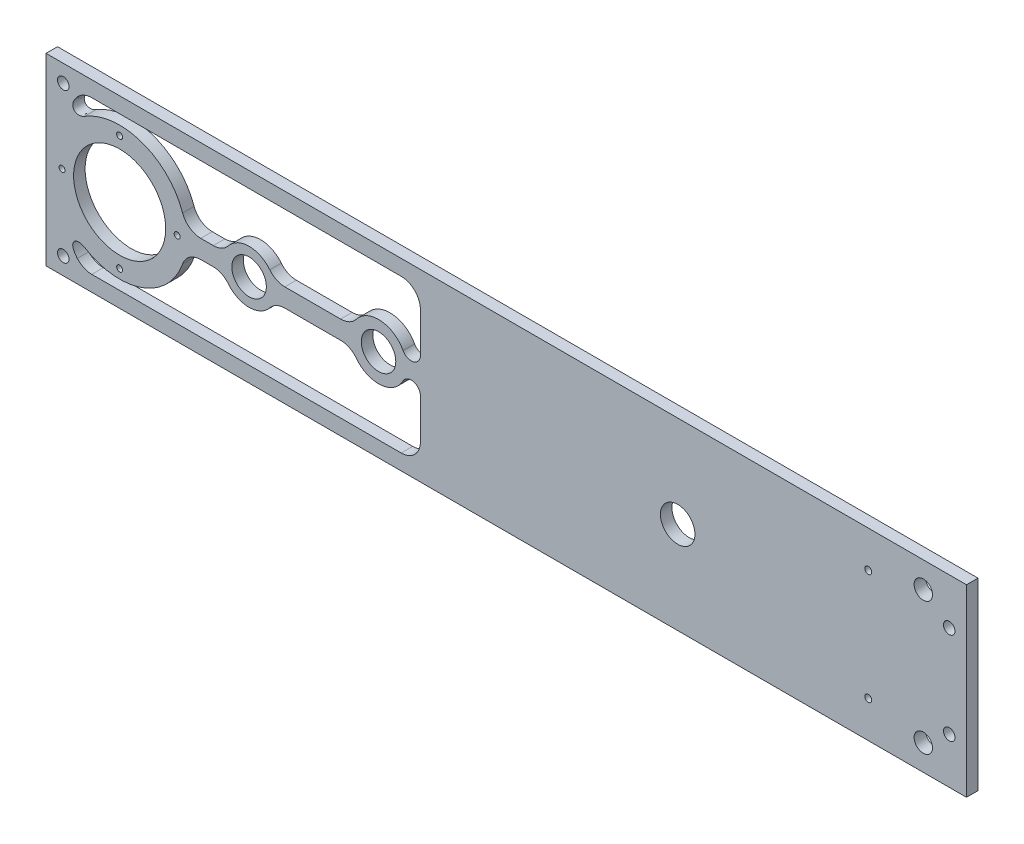
SolidWorks part; units mm, degrees
material "1060 Alloy"
ref_plane "Front Plane" through (0, 0, 0) normal (0, 0, 1) x (1, 0, 0)
ref_plane "Top Plane" through (0, 0, 0) normal (0, 1, 0) x (1, 0, 0)
ref_plane "Right Plane" through (0, 0, 0) normal (1, 0, 0) x (0, 0, -1)
sketch "Sketch1" plane through (0, 0, 0) normal (0, 0, 1) x (1, 0, 0)
  line L1 (0, 50.8) -> (508, 50.8)
  line L2 (0, 50.8) -> (0, -50.8)
  line L3 (0, -50.8) -> (508, -50.8)
  line L4 (508, 50.8) -> (508, -50.8)
  dimension "D1" = 508
  dimension "D2" = 101.6
extrude "Boss-Extrude1" add sketch "Sketch1" against normal blind 6.35
sketch "Sketch2" plane through (0, 0, 0) normal (0, 0, 1) x (1, 0, 0)
  line L0 (0, 50.8) -> (0, -50.8) construction
  circle A0 centre (40.64, 0) radius 25.4
  circle A1 centre (72.39, 0) radius 1.651
  circle A2 centre (40.64, -31.75) radius 1.651
  circle A3 centre (8.89, 0) radius 1.651
  circle A4 centre (40.64, 31.75) radius 1.651
  point P15 (40.64, 0)
  dimension "D1" = 50.8
  dimension "D2" = 3.302
  dimension "D3" = 31.75
  dimension "D4" = 40.64
  dimension "D5" = 4
extrude "Motor mount" cut sketch "Sketch2" against normal blind 6.35
sketch "Sketch3" plane through (0, 0, 0) normal (0, 0, 1) x (1, 0, 0)
  line L0 (398.315, 0) -> (50398.315, 0) construction
  circle A0 centre (40.64, 0) radius 25.4 construction
  circle A1 centre (40.64, 0) radius 25.4 construction
  circle A2 centre (112.0775, 0) radius 9.525
  circle A3 centre (183.515, 0) radius 9.525
  circle A4 centre (348.615, 0) radius 9.525
  circle A5 centre (453.8064, -30.5822) radius 47.9695 construction
  circle A6 centre (484.1695, -36.5735) radius 93.3199 construction
  circle A7 centre (453.8064, -30.5822) radius 47.9695 construction
  circle A8 centre (484.1695, -36.5735) radius 93.3199 construction
  circle A9 centre (453.8064, -30.5822) radius 1.905
  circle A10 centre (484.1695, -36.5735) radius 5.08
  circle A11 centre (484.1695, 36.5735) radius 5.08
  circle A12 centre (453.8064, 30.5822) radius 1.905
  dimension "D1" = 19.05
  dimension "D2" = 19.05
  dimension "D5" = 19.05
  dimension "D7" = 10.16
  dimension "D8" = 3.81
  dimension "D3" = 71.4375
  dimension "D4" = 71.4375
  dimension "D6" = 165.1
extrude "Cut-Extrude2" cut sketch "Sketch3" against normal through all
sketch "Sketch4" plane through (0, 0, 0) normal (0, 0, 1) x (1, 0, 0)
  line L0 (508, 50.8) -> (0, 50.8) construction
  line L1 (0, 50.8) -> (0, -50.8) construction
  line L2 (508, -50.8) -> (508, 50.8) construction
  line L3 (0, -50.8) -> (508, -50.8) construction
  circle A0 centre (9.525, 41.275) radius 3.175
  circle A1 centre (9.525, -41.275) radius 3.175
  circle A2 centre (498.475, 25.4) radius 3.175
  circle A3 centre (498.475, -25.4) radius 3.175
  dimension "D1" = 6.35
  dimension "D2" = 6.35
  dimension "D3" = 6.35
  dimension "D4" = 6.35
  dimension "D5" = 9.525
  dimension "D6" = 9.525
  dimension "D7" = 9.525
  dimension "D8" = 25.4
  dimension "D9" = 9.525
  dimension "D10" = 25.4
extrude "Cut-Extrude3" cut sketch "Sketch4" against normal through all
sketch "Sketch7" plane through (0, 0, 0) normal (0, 0, 1) x (1, 0, 0)
  line L3 (211.7063, 0) -> (211.7063, 47.2876) construction
  line L5 (211.7063, 47.2876) -> (0, 47.2876) construction
  line L6 (0, 47.2876) -> (0, 0) construction
  line L7 (0, 0) -> (40.64, 0) construction
  line L8 (40.64, -5.08) -> (112.0775, -5.08)
  line L9 (112.0775, -5.08) -> (183.515, -5.08)
  line L10 (183.515, -5.08) -> (216.7863, -5.08)
  line L11 (216.7863, -5.08) -> (216.7863, 52.3676)
  line L12 (216.7863, 52.3676) -> (-5.08, 52.3676)
  line L13 (-5.08, 52.3676) -> (-5.08, -5.08)
  line L14 (-5.08, -5.08) -> (40.64, -5.08)
  line L15 (85.4063, 5.08) -> (92.3414, 5.08)
  line L16 (131.8136, 5.08) -> (162.5851, 5.08)
  line L18 (206.6263, 9.6628) -> (206.6263, 31.6032)
  line L19 (196.0219, 42.2076) -> (25.2631, 42.2076)
  line L20 (0, 50.8) -> (0, -50.8) construction
  line L22 (206.6263, 5.08) -> (206.6263, 42.2076) construction
  line L23 (112.0775, 5.08) -> (183.515, 5.08) construction
  line L24 (40.64, 5.08) -> (112.0775, 5.08) construction
  line L25 (206.6263, 42.2076) -> (5.08, 42.2076) construction
  line L26 (5.08, 42.2076) -> (5.08, 5.08) construction
  line L27 (112.0775, 0) -> (183.515, 0) construction
  line L28 (40.64, 0) -> (112.0775, 0) construction
  line L29 (183.515, 0) -> (211.7063, 0) construction
  line L30 (5.08, 5.08) -> (40.64, 5.08) construction
  line L31 (183.515, 5.08) -> (206.6263, 5.08) construction
  circle A0 centre (40.64, 0) radius 31.75 construction
  circle A1 centre (112.0775, 0) radius 9.525
  circle A2 centre (183.515, 0) radius 9.525
  circle A3 centre (9.525, 41.275) radius 3.1307
  arc A4 (100.6434, 9.0867) -> (92.3414, 5.08) centre (92.3414, 15.6844) cw
  arc A5 (197.0687, 7.2633) -> (206.6263, 9.6628) centre (201.5463, 9.6628) ccw
  arc A6 (17.2833, 38.5871) -> (25.2631, 42.2076) centre (25.2631, 31.6032) cw
  arc A7 (206.6263, 31.6032) -> (196.0219, 42.2076) centre (196.0219, 31.6032) ccw
  circle A8 centre (112.0775, 0) radius 4.445
  circle A9 centre (183.515, 0) radius 4.445
  circle A10 centre (40.64, 0) radius 26.67
  arc A11 (197.0687, 7.2633) -> (171.333, 9.3838) centre (183.515, 0) ccw
  arc A12 (162.5851, 5.08) -> (171.333, 9.3838) centre (162.5851, 16.1223) ccw
  arc A13 (123.5116, 9.0867) -> (100.6434, 9.0867) centre (112.0775, 0) ccw
  arc A14 (131.8136, 5.08) -> (123.5116, 9.0867) centre (131.8136, 15.6844) cw
  arc A15 (75.3984, 12.178) -> (21.2634, 31.3209) centre (40.64, 0) ccw
  arc A17 (75.3984, 12.178) -> (85.4063, 5.08) centre (85.4063, 15.6844) ccw
  spline S0 degree 3 poles (17.2833, 38.5871) (11.5305, 32.014) (16.7871, 28.5516) (21.2634, 31.3209) knots 0 0 0 0 1 1 1 1
  dimension "D1" = 5.08
  dimension "D3" = 5.08
  dimension "D4" = 11.0423
  dimension "D5" = 10.6044
  dimension "D6" = 10.6044
  dimension "D7" = 10.6044
  dimension "D2" = 5.08
extrude "Cut-Extrude4" cut sketch "Sketch7" against normal through all contours L19 A6 S0 A15 A17 L15 A4 A13 A14 L16 A12 A11 A5 L18 A7
mirror "Mirror1" about plane through (0, 0, 0) normal (0, 1, 0) of "Cut-Extrude4"
